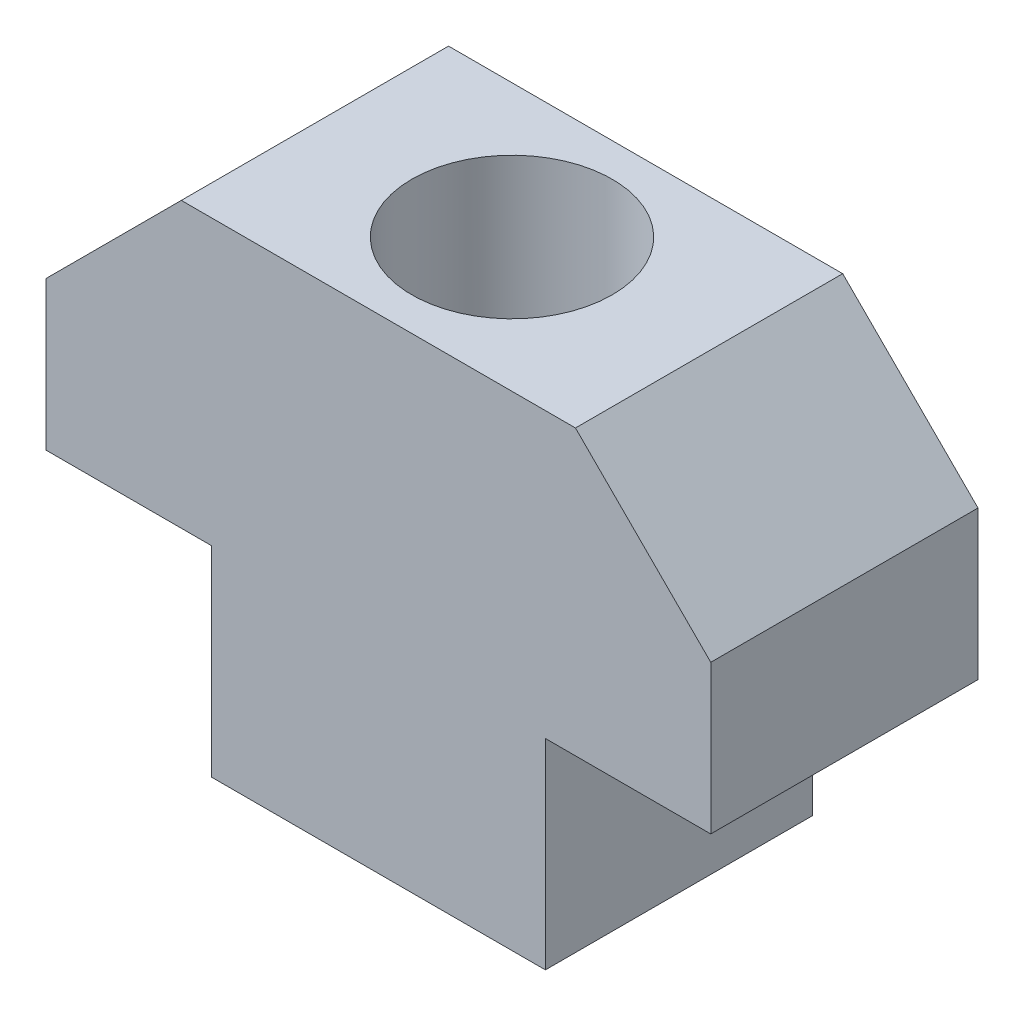
SolidWorks part; units mm, degrees
note: '?' marks a value the reader was unsure of.
ref_plane "Front Plane" through (0, 0, 0) normal (0, 0, 1) x (1, 0, 0)
ref_plane "Top Plane" through (0, 0, 0) normal (0, 1, 0) x (1, 0, 0)
ref_plane "Right Plane" through (0, 0, 0) normal (1, 0, 0) x (0, 0, -1)
sketch "Sketch1" plane through (0, 0, 0) normal (0, 0, 1) x (1, 0, 0)
  line L0 (-5, 0) -> (5, 0)
  line L1 (0, 14.9232) -> (0, -1.1506) construction
  line L2 (5, 0) -> (5, 6)
  line L3 (5, 6) -> (9.95, 6)
  line L4 (9.95, 6) -> (9.95, 10.45)
  line L5 (9.95, 10.45) -> (5.9, 14.5)
  line L6 (5.9, 14.5) -> (-5.9, 14.5)
  line L8 (-5.9, 14.5) -> (-9.95, 10.45)
  line L9 (-9.95, 10.45) -> (-9.95, 6)
  line L10 (-9.95, 6) -> (-5, 6)
  line L11 (-5, 6) -> (-5, 0)
  dimension "D1" = 6
  dimension "D2" = 10
  dimension "D3" = 14.5
  dimension "D4" = 19.9
  dimension "D5" = 135
  dimension "D6" = 11.8
extrude "Extrude1" add sketch "Sketch1" along normal mid plane 8
sketch "Sketch2" plane through (0, 0, 0) normal (0, 1, 0) x (1, 0, 0)
  circle A0 centre (0, 0) radius 3
  dimension "D1" = 6
extrude "Cut-Extrude1" cut sketch "Sketch2" along normal up to next
cosmetic thread "Cosmetic Thread1" parameters "D2"=6.001
fillet "Fillet1" [suppressed] radius 2?
